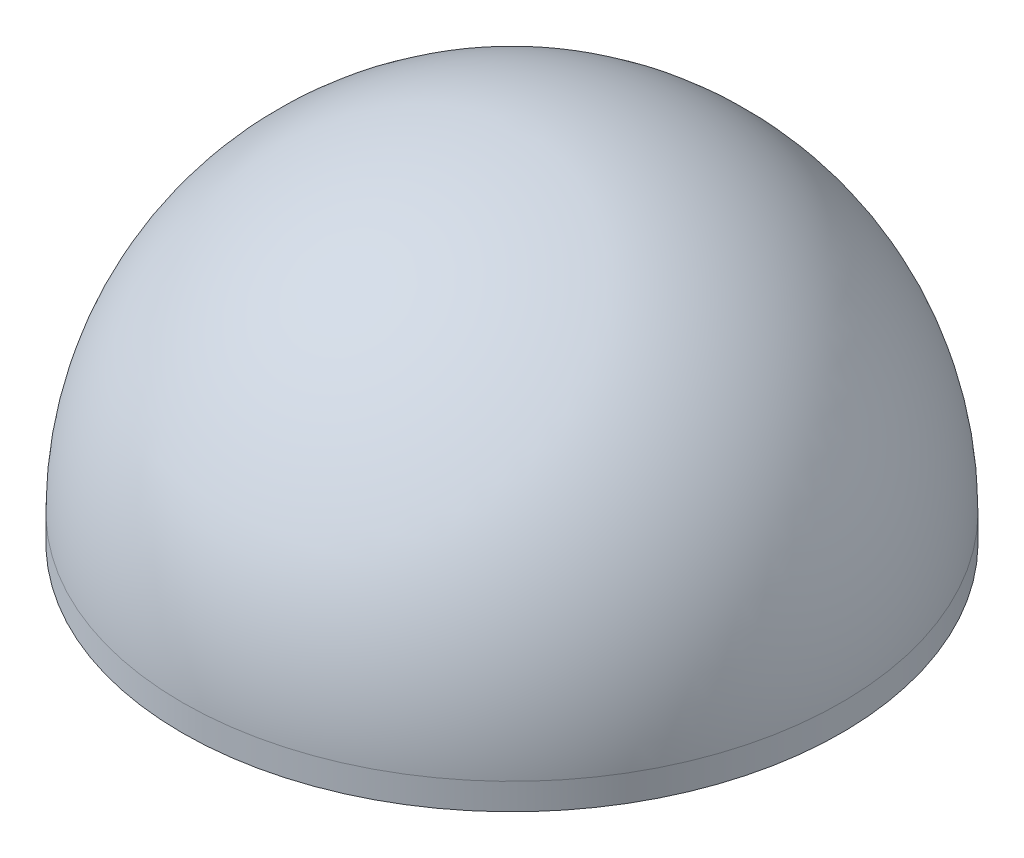
SolidWorks part; units mm, degrees
ref_plane "Front Plane" through (0, 0, 0) normal (0, 0, 1) x (1, 0, 0)
ref_plane "Top Plane" through (0, 0, 0) normal (0, 1, 0) x (1, 0, 0)
ref_plane "Right Plane" through (0, 0, 0) normal (1, 0, 0) x (0, 0, -1)
sketch "Sketch1" plane through (0, 0, 0) normal (0, 1, 0) x (1, 0, 0)
  circle A0 centre (0, 0) radius 25
  dimension "D1" = 50
extrude "Boss-Extrude1" add sketch "Sketch1" along normal blind 2
dome "Dome1" faces to dome 1 distance 25 reverse direction no elliptical dome no face at (0, 2, 25) parameters "D1"=25
shell "Shell1" thickness 2 removed face at (0, 0, 25)
equation "\"alien_lid_diameter\"= 50mm"
equation "\"alien_lid_radius\"= \"alien_lid_diameter\" / 2"
equation "\"D1@Sketch1\"=\"alien_lid_diameter\""
